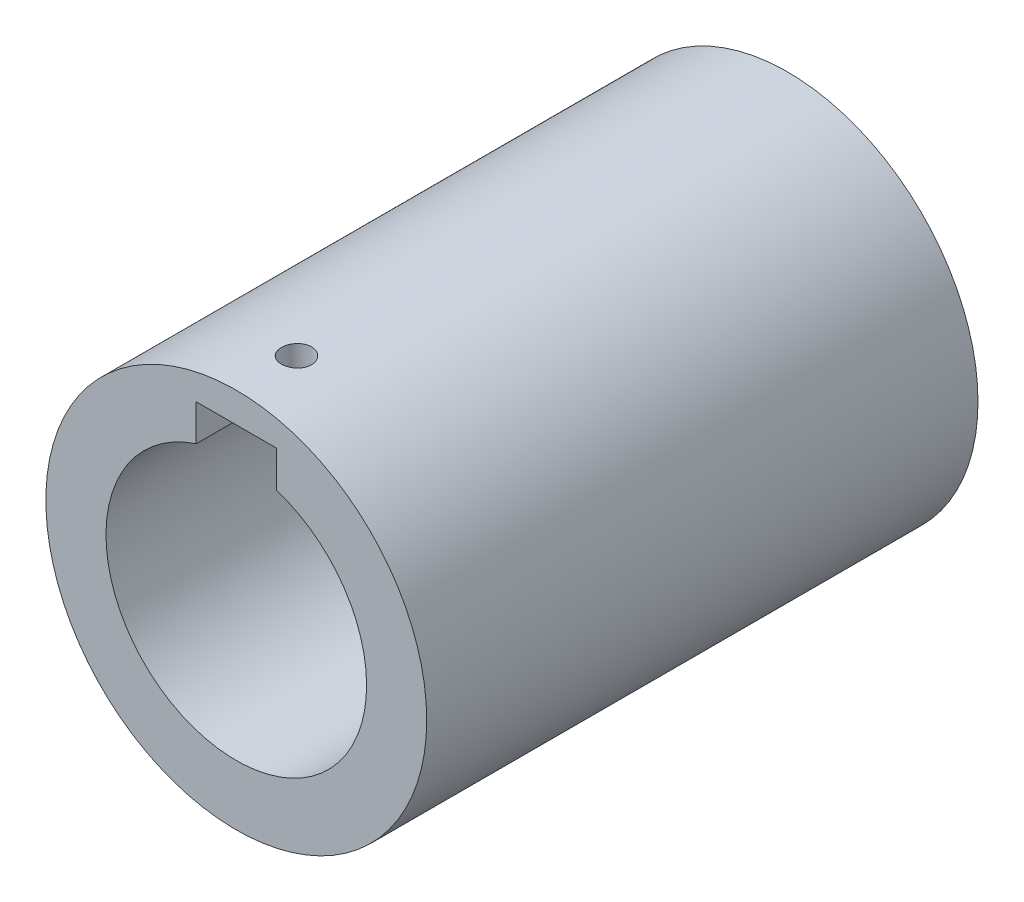
SolidWorks part; units mm, degrees
ref_plane "Front Plane" through (0, 0, 0) normal (0, 0, 1) x (1, 0, 0)
ref_plane "Top Plane" through (0, 0, 0) normal (0, 1, 0) x (1, 0, 0)
ref_plane "Right Plane" through (0, 0, 0) normal (1, 0, 0) x (0, 0, -1)
sketch "Sketch1" plane through (0, 0, 0) normal (0, 0, 1) x (1, 0, 0)
  circle A0 centre (0, 0) radius 13
  circle A1 centre (0, 0) radius 19
  dimension "D1" = 38
  dimension "D2" = 26
extrude "Boss-Extrude1" add sketch "Sketch1" along normal blind 55
sketch "Sketch2" plane through (0, 0, 55) normal (0, 0, 1) x (1, 0, 0)
  line L1 (-4, 16) -> (4, 16)
  line L2 (-4, 16) -> (-4, 10)
  line L3 (-4, 10) -> (4, 10)
  line L4 (4, 16) -> (4, 10)
  line L5 (-4, 16) -> (4, 10) construction
  line L6 (-4, 10) -> (4, 16) construction
  circle A0 centre (0, 0) radius 13 construction
  point P0 (0, 13)
  dimension "D1" = 8
  dimension "D2" = 6
extrude "Cut-Extrude3" cut sketch "Sketch2" against normal blind 24
fillet "Fillet5" radius 4 1 edges at (4, 14.1847, 31)
fillet "Fillet6" radius 4 1 edges at (-4, 14.1847, 31)
sketch "Sketch3" plane through (0, 16, 0) normal (0, -1, 0) x (-1, 0, 0)
  line L0 (0, -31) -> (0, -55) construction
  line L1 (-4, -55) -> (4, -55) construction
  circle A0 centre (0, -49) radius 1.5
  dimension "D2" = 3
  dimension "D1" = 6
extrude "Cut-Extrude11" cut sketch "Sketch3" against normal through all
